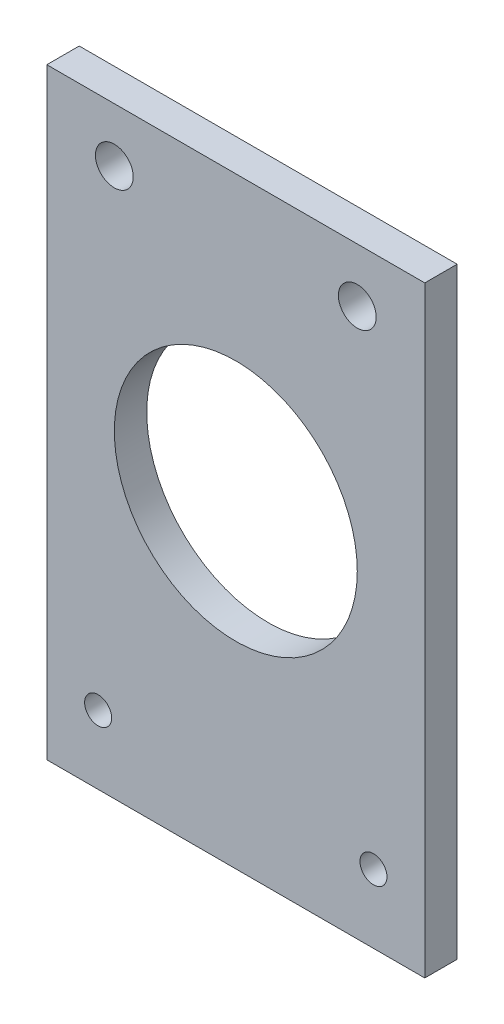
SolidWorks part; units mm, degrees
ref_plane "Front Plane" through (0, 0, 0) normal (0, 0, 1) x (1, 0, 0)
ref_plane "Top Plane" through (0, 0, 0) normal (0, 1, 0) x (1, 0, 0)
ref_plane "Right Plane" through (0, 0, 0) normal (1, 0, 0) x (0, 0, -1)
sketch "Sketch2" plane through (0, 0, 0) normal (0, 0, 1) x (1, 0, 0)
  line L0 (-55, 49.5) -> (55, 49.5) construction
  line L1 (-35, 0) -> (35, 0)
  line L2 (-35, 0) -> (-35, 59)
  line L3 (-35, 59) -> (35, 59) construction
  line L4 (35, 0) -> (35, 59)
  line L5 (0, 49.5) -> (0, 0) construction
  line L6 (0, 49.5) -> (0, 59) construction
  line L10 (35, 91.5) -> (-35, 91.5) construction
  line L11 (35, 59) -> (35, 91.5)
  line L12 (35, 91.5) -> (-35, 91.5) construction
  line L13 (-35, 91.5) -> (-35, 59)
  line L14 (35, 91.5) -> (35, 111.5)
  line L15 (35, 111.5) -> (-35, 111.5)
  line L16 (-35, 91.5) -> (-35, 111.5)
  circle A0 centre (-55, 49.5) radius 3 construction
  circle A1 centre (55, 49.5) radius 3 construction
  circle A2 centre (-55, 49.5) radius 16 construction
  circle A3 centre (55, 49.5) radius 16 construction
  circle A6 centre (0, 59) radius 22.5
  point P6 (0, 0)
  dimension "D1" = 6
  dimension "D2" = 32
  dimension "D5" = 45
  dimension "D9" = 20
  dimension "D3" = 110
  dimension "D4" = 9.5
  dimension "D6" = 70
  dimension "D7" = 49.5
  dimension "D8" = 32.5
extrude "Boss-Extrude1" add sketch "Sketch2" along normal mid plane 6
sketch "Sketch3" plane through (0, 0, 3) normal (0, 0, 1) x (1, 0, 0)
  line L0 (-22.5, 101.5) -> (22.5, 101.5) construction
  line L1 (-35, 0) -> (-25.5, 0) construction
  line L2 (-35, 0) -> (-35, 12.7) construction
  line L3 (-35, 12.7) -> (-25.5, 12.7) construction
  line L4 (-25.5, 0) -> (-25.5, 12.7) construction
  line L5 (35, 0) -> (25.5, 0) construction
  line L6 (35, 0) -> (35, 12.7) construction
  line L7 (35, 12.7) -> (25.5, 12.7) construction
  line L8 (25.5, 0) -> (25.5, 12.7) construction
  line L9 (0, 101.5) -> (0, 111.5) construction
  line L10 (35, 111.5) -> (-35, 111.5) construction
  circle A0 centre (-25.5, 12.7) radius 2.5
  circle A1 centre (25.5, 12.7) radius 2.5
  circle A2 centre (-22.5, 101.5) radius 3.5
  circle A3 centre (22.5, 101.5) radius 3.5
  point P19 (0, 101.5)
  dimension "D1" = 12.7
  dimension "D2" = 5
  dimension "D4" = 7
  dimension "D3" = 9.5
  dimension "D5" = 10
  dimension "D6" = 45
extrude "Cut-Extrude1" cut sketch "Sketch3" against normal blind 6
